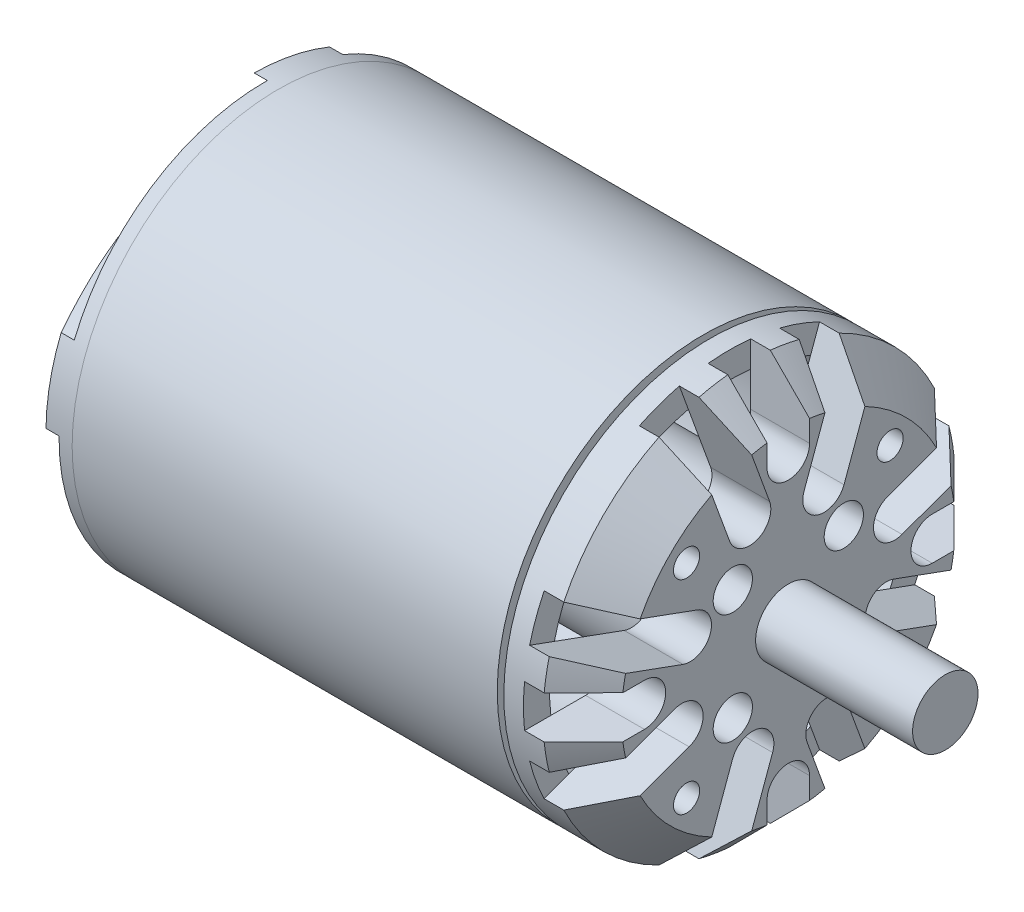
SolidWorks part; units mm, degrees
ref_plane "Front Plane" through (0, 0, 0) normal (0, 0, 1) x (1, 0, 0)
ref_plane "Top Plane" through (0, 0, 0) normal (0, 1, 0) x (1, 0, 0)
ref_plane "Right Plane" through (0, 0, 0) normal (1, 0, 0) x (0, 0, -1)
sketch "Sketch1" plane through (0, 0, 0) normal (1, 0, 0) x (0, 0, -1)
  circle A0 centre (0, 0) radius 31.5
  dimension "D1" = 63
extrude "Extrude1" add sketch "Sketch1" along normal blind 92
sketch "Sketch2" plane through (92, 0, 0) normal (1, 0, 0) x (0, 0, -1)
  circle A0 centre (0, 0) radius 5
  dimension "D1" = 10
extrude "Extrude2" add sketch "Sketch2" along normal blind 24
sketch "Sketch3" plane through (92, 0, 0) normal (1, 0, 0) x (0, 0, -1)
  line L0 (0, 0) -> (-18.75, 0)
  line L1 (0, 0) -> (-11.946, 4.348)
  line L2 (0, 0) -> (-13.222, -4.8124)
  line L3 (-17.3875, -2.87) -> (-30.5539, -7.6621)
  line L4 (-22, 3.25) -> (-33.5804, 3.25)
  line L5 (-2.87, 17.3875) -> (-7.6621, 30.5539)
  line L6 (-22, -3.25) -> (-33.5804, -3.25)
  line L7 (-33.5804, 3.25) -> (-33.5804, -3.25)
  line L8 (-15.1644, -8.978) -> (-28.3308, -13.7701)
  line L9 (-16.1116, 2.4056) -> (-30.5539, 7.6621)
  line L10 (-13.8884, 8.5136) -> (-28.3308, 13.7701)
  line L11 (3.25, 22) -> (3.25, 33.5804)
  line L12 (-3.25, 22) -> (-3.25, 33.5804)
  line L13 (3.25, 33.5804) -> (-3.25, 33.5804)
  line L14 (-8.978, 15.1644) -> (-13.7701, 28.3308)
  line L15 (2.4056, 16.1116) -> (7.6621, 30.5539)
  line L16 (8.5136, 13.8884) -> (13.7701, 28.3308)
  line L17 (17.3875, 2.87) -> (30.5539, 7.6621)
  line L18 (22, -3.25) -> (33.5804, -3.25)
  line L19 (22, 3.25) -> (33.5804, 3.25)
  line L20 (33.5804, -3.25) -> (33.5804, 3.25)
  line L21 (15.1644, 8.978) -> (28.3308, 13.7701)
  line L22 (16.1116, -2.4056) -> (30.5539, -7.6621)
  line L23 (13.8884, -8.5136) -> (28.3308, -13.7701)
  line L24 (2.87, -17.3875) -> (7.6621, -30.5539)
  line L25 (-3.25, -22) -> (-3.25, -33.5804)
  line L26 (3.25, -22) -> (3.25, -33.5804)
  line L27 (-3.25, -33.5804) -> (3.25, -33.5804)
  line L28 (8.978, -15.1644) -> (13.7701, -28.3308)
  line L29 (-2.4056, -16.1116) -> (-7.6621, -30.5539)
  line L30 (-8.5136, -13.8884) -> (-13.7701, -28.3308)
  arc A0 (-22, -3.25) -> (-22, 3.25) centre (-22, 0) ccw
  circle A1 centre (0, 0) radius 31.5 construction
  arc A2 (-16.1116, 2.4056) -> (-13.8884, 8.5136) centre (-15, 5.4596) ccw
  arc A3 (-15.1644, -8.978) -> (-17.3875, -2.87) centre (-16.276, -5.924) ccw
  arc A4 (-3.25, 22) -> (3.25, 22) centre (0, 22) ccw
  arc A5 (2.4056, 16.1116) -> (8.5136, 13.8884) centre (5.4596, 15) ccw
  arc A6 (-8.978, 15.1644) -> (-2.87, 17.3875) centre (-5.924, 16.276) ccw
  arc A7 (22, 3.25) -> (22, -3.25) centre (22, 0) ccw
  arc A8 (16.1116, -2.4056) -> (13.8884, -8.5136) centre (15, -5.4596) ccw
  arc A9 (15.1644, 8.978) -> (17.3875, 2.87) centre (16.276, 5.924) ccw
  arc A10 (3.25, -22) -> (-3.25, -22) centre (0, -22) ccw
  arc A11 (-2.4056, -16.1116) -> (-8.5136, -13.8884) centre (-5.4596, -15) ccw
  arc A12 (8.978, -15.1644) -> (2.87, -17.3875) centre (5.924, -16.276) ccw
  circle M1 centre (0, 0) radius 31.5
  dimension "D1" = 6.5
  dimension "D5" = 6.5
  dimension "D7" = 6.5
  dimension "D2" = 22
  dimension "D3" = 20
  dimension "D4" = 20
  dimension "D6" = 15
extrude "Extrude3" cut sketch "Sketch3" against normal blind 9 contours A0 L4 L6 M1 | L9 A2 L10 M1 | A3 L3 L8 M1 | L29 A11 L30 M1 | L26 A10 L25 M1 | L28 A12 L24 M1 | L22 A8 L23 M1 | L19 A7 L18 M1 | L21 A9 L17 M1 | L15 A5 L16 M1 | L12 A4 L11 M1 | L14 A6 L5 M1 region at (92, 0, 25.4239) region at (92, 7.6655, 21.0609) region at (92, -7.8973, 21.6978) region at (92, 21.6978, 7.8973) region at (92, -21.0609, 7.6655) region at (92, 25.4239, 0) region at (92, -25.4239, 0) region at (92, 21.0609, -7.6655) region at (92, -21.6978, -7.8973) region at (92, 7.8973, -21.6978) region at (92, -7.6655, -21.0609) region at (92, 0, -25.4239)
chamfer "Chamfer1" distance 6 angle 45 12 edges at (92, 5.4699, 31.0214) (92, -5.4699, 31.0214) (92, -22.2739, 22.2739) (92, -31.0214, 5.4699) (92, -31.0214, -5.4699) (92, -22.2739, -22.2739) (92, -5.4699, -31.0214) (92, 5.4699, -31.0214) (92, 22.2739, -22.2739) (92, 31.0214, -5.4699) (92, 31.0214, 5.4699) (92, 22.2739, 22.2739)
sketch "Sketch4" plane through (0, 0, 0) normal (-1, 0, 0) x (0, 0, 1)
  circle A0 centre (0, 0) radius 14.5
  circle A1 centre (0, 0) radius 31.5
  dimension "D1" = 29
extrude "Extrude4" cut sketch "Sketch4" against normal blind 3
sketch "Sketch5" plane through (3, 0, 0) normal (-1, 0, 0) x (0, 0, 1)
  circle A0 centre (-24, 0) radius 7.5
  circle A1 centre (0, 0) radius 31.5 construction
  arc A2 (-16.5, 0) -> (-11.8663, 29.1795) centre (43.4985, 5.4299) cw
  arc A3 (-11.8663, 29.1795) -> (-31.5, 0) centre (0, 0) ccw
  circle A4 centre (0, 24) radius 7.5
  arc A5 (0, 16.5) -> (29.1795, 11.8663) centre (5.4299, -43.4985) cw
  arc A6 (29.1795, 11.8663) -> (0, 31.5) centre (0, 0) ccw
  circle A7 centre (24, 0) radius 7.5
  arc A8 (16.5, 0) -> (11.8663, -29.1795) centre (-43.4985, -5.4299) cw
  arc A9 (11.8663, -29.1795) -> (31.5, 0) centre (0, 0) ccw
  circle A10 centre (0, -24) radius 7.5
  arc A11 (0, -16.5) -> (-29.1795, -11.8663) centre (-5.4299, 43.4985) cw
  arc A12 (-29.1795, -11.8663) -> (0, -31.5) centre (0, 0) ccw
  circle M2 centre (0, 0) radius 31.5
  dimension "D1" = 15
extrude "Extrude5" cut sketch "Sketch5" against normal blind 9 contours A0 A2 | A0 A2 M2 | A4 A5 | A4 A5 M2 | A7 A8 | A7 A8 M2 | A10 A11 | A10 A11 M2 region at (3, -0.0001, -24.0009) region at (3, 15.0114, -21.202) region at (3, -21.202, -15.0114) region at (3, 21.202, 15.0114) region at (3, 24.0009, -0.0001) region at (3, -24.0009, 0.0001) region at (3, -15.0114, 21.202) region at (3, 0.0001, 24.0009)
chamfer "Chamfer2" distance 7 angle 64 4 edges at (3, -30.9144, 6.0455) (3, 6.0455, 30.9144) (3, 30.9144, -6.0455) (3, -6.0455, -30.9144) first distance on face at (84.5, 0, 0)
sketch "Sketch7" plane through (12, 0, 0) normal (-1, 0, 0) x (0, 0, 1)
  circle A0 centre (0, 0) radius 27.5
  circle A1 centre (0, 0) radius 12.5
  arc A2 (29.1795, 11.8663) -> (0, 31.5) centre (0, 0) ccw construction
  dimension "D1" = 4
  dimension "D2" = 15
extrude "Extrude6" cut sketch "Sketch7" against normal up to surface (71 mm away) up to face at (83, 22.1351, 8.0565)
sketch "Sketch8" plane through (0, 0, 0) normal (0, 0, 1) x (1, 0, 0)
  line L0 (83, 31.5) -> (12, 31.5) construction
  line L1 (80, 31.5) -> (79, 31.5)
  line L2 (80, 31.5) -> (80, 27.5)
  line L3 (80, 27.5) -> (79, 27.5)
  line L4 (79, 31.5) -> (79, 27.5)
  line L5 (92, 11.7044) -> (92, 22.6552) construction
  line L6 (116, 0) -> (-4.408, 0)
  line L7 (116, -5) -> (116, 5) construction
  dimension "D1" = 12
  dimension "D2" = 1
  dimension "D3" = 4
revolve "Cut-Revolve1" cut sketch "Sketch8" angle 360 about L6 region at (79.5, 29.5, 0)
sketch "Sketch10" plane through (0, 0, 0) normal (-1, 0, 0) x (0, 0, 1)
  circle A0 centre (0, 0) radius 31.5
  circle A1 centre (0, 0) radius 31.494
  dimension "D1" = 0.006
extrude "Extrude7" cut sketch "Sketch10" against normal blind 14
sketch "Sketch11" plane through (92, 0, 0) normal (1, 0, 0) x (0, 0, -1)
  line L0 (0, 0) -> (-16.5, 0) construction
  line L1 (0, 0) -> (-14.7318, 14.7318) construction
  circle A0 centre (-15.5563, 15.5563) radius 2
  circle A1 centre (-8.4853, 8.4853) radius 3
  circle A2 centre (15.5563, 15.5563) radius 2
  circle A3 centre (8.4853, 8.4853) radius 3
  circle A4 centre (15.5563, -15.5563) radius 2
  circle A5 centre (8.4853, -8.4853) radius 3
  circle A6 centre (-15.5563, -15.5563) radius 2
  circle A7 centre (-8.4853, -8.4853) radius 3
  dimension "D3" = 4
  dimension "D5" = 6
  dimension "D1" = 45
  dimension "D2" = 22
  dimension "D4" = 12
extrude "Extrude8" cut sketch "Sketch11" against normal up to surface (9 mm away) up to face at (83, 0, 0)
